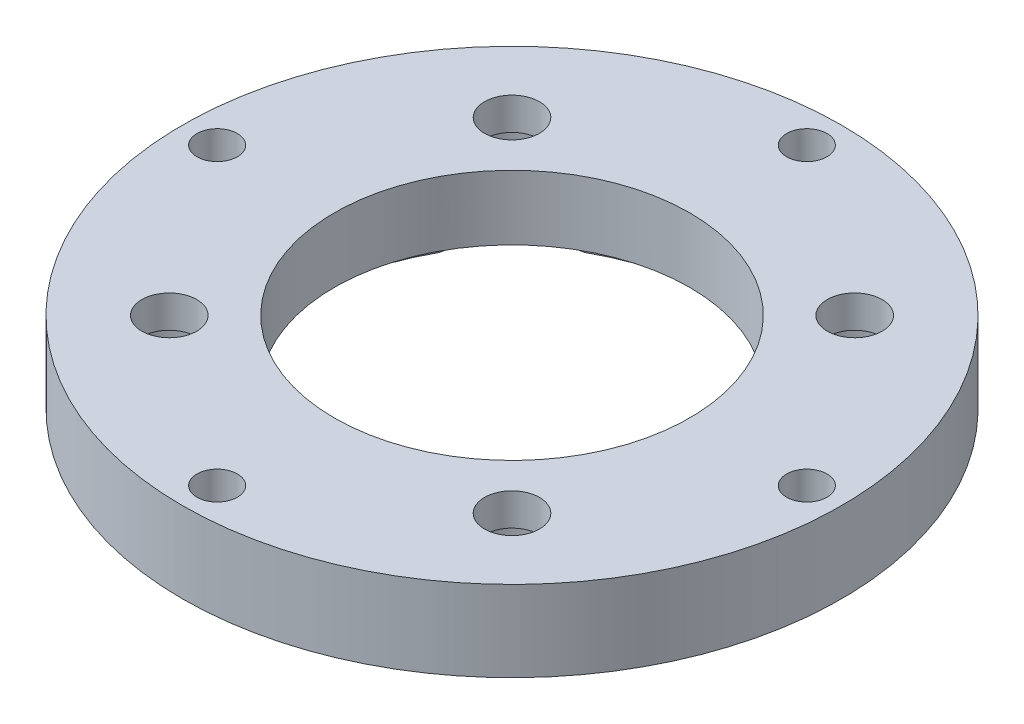
SolidWorks part; units mm, degrees
material "3.1355 (EN-AW 2024)"
ref_plane "Front" through (0, 0, 0) normal (0, 0, 1) x (1, 0, 0)
ref_plane "Top" through (0, 0, 0) normal (0, 1, 0) x (1, 0, 0)
ref_plane "Right" through (0, 0, 0) normal (1, 0, 0) x (0, 0, -1)
sketch "Эскиз1" plane through (0, 0, 0) normal (0, 1, 0) x (1, 0, 0)
  circle A0 centre (0, 0) radius 20.4
  circle A1 centre (0, 0) radius 11
  dimension "D1" = 40.8
  dimension "D2" = 22
extrude "Бобышка-Вытянуть1" add sketch "Эскиз1" along normal blind 5
sketch "Эскиз2" plane through (0, 5, 0) normal (0, 1, 0) x (1, 0, 0)
  circle A0 centre (0, 0) radius 18.25 construction
  point P3 (0, 18.25)
  point P4 (18.25, 0)
  point P5 (0, -18.25)
  point P6 (-18.25, 0)
  dimension "D1" = 36.5
hole_wizard "Отверстие обработанное метчиком M3x0.51" positions "Эскиз5" profile "Эскиз4" tap size "M3x0.5" standard "Ansi Metric" end condition through all
sketch "Эскиз5" plane through (0, 5, 0) normal (0, 1, 0) x (1, 0, 0)
  point P0 (-18.25, 0)
  point P3 (0, 18.25)
  point P6 (18.25, 0)
  point P9 (0, -18.25)
sketch "Эскиз4" plane through (-18.25, 5, 0) normal (1, 0, 0) x (0, 0, 1)
  line L0 (0, 0) -> (0, 5)
  line L1 (0, 5) -> (1.25, 5)
  line L2 (1.25, 5) -> (1.25, 0)
  line L5 (1.25, 0) -> (0, 0)
  line L11 (0, -6.35) -> (0, 107.95) construction
  dimension "Диаметр проходного сверла" = 2.5
  dimension "Глубина проходного сверла" = 5
cosmetic thread "Отверстие резьбы1"
cosmetic thread "Отверстие резьбы2"
cosmetic thread "Отверстие резьбы3"
cosmetic thread "Отверстие резьбы4"
sketch "Эскиз6" plane through (0, 0, 0) normal (0, -1, 0) x (1, 0, 0)
  line L0 (0, 0) -> (-10.6066, 10.6066) construction
  line L1 (0, 0) -> (-15, 0) construction
  line L2 (0, 0) -> (10.6066, 10.6066) construction
  line L3 (0, 0) -> (10.6066, -10.6066) construction
  line L4 (0, 0) -> (-10.6066, -10.6066) construction
  circle A0 centre (0, 0) radius 15 construction
  point P11 (0, 0)
  dimension "D1" = 30
  dimension "D2" = 45
  dimension "D3" = 4
hole_wizard "Цековка для винта с внутренним шестигранником M31" positions "Эскиз8" profile "Эскиз7" counterbore size "M3" standard "Ansi Metric" end condition through all
sketch "Эскиз8" plane through (0, 0, 0) normal (0, -1, 0) x (-1, 0, 0)
  point P0 (10.6066, -10.6066)
  point P3 (-10.6066, -10.6066)
  point P6 (-10.6066, 10.6066)
  point P9 (10.6066, 10.6066)
sketch "Эскиз7" plane through (-10.6066, 0, 10.6066) normal (1, 0, 0) x (0, 0, -1)
  line L0 (0, 0) -> (0, 5)
  line L1 (0, 5) -> (1.7, 5)
  line L3 (1.7, 5) -> (1.7, 3)
  line L4 (1.7, 3) -> (3.25, 3)
  line L5 (3.25, 3) -> (3.25, 0)
  line L7 (3.25, 0) -> (0, 0)
  line L11 (0, -6.35) -> (0, 107.95) construction
  dimension "Диаметр сквозного отверстия" = 3.4
  dimension "Глубина сквозного отверстия" = 5
  dimension "Диаметр цековки" = 6.5
  dimension "Глубина цековки" = 3
sketch "Эскиз9" plane through (0, 0, 0) normal (0, -1, 0) x (1, 0, 0)
  circle A0 centre (0, 0) radius 12.25
  dimension "D1" = 24.5
extrude "Вырез-Вытянуть1" cut sketch "Эскиз9" against normal blind 1
fillet "Скругление1" radius 1 8 edges at (-9.6959, 0.5, -7.4868) (-7.4868, 0.5, -9.6959) (7.4868, 0.5, -9.6959) (9.6959, 0.5, -7.4868) (9.6959, 0.5, 7.4868) (7.4868, 0.5, 9.6959) (-9.6959, 0.5, 7.4868) (-7.4868, 0.5, 9.6959)
equation "\"D1@Эскиз2\"=36.5"
